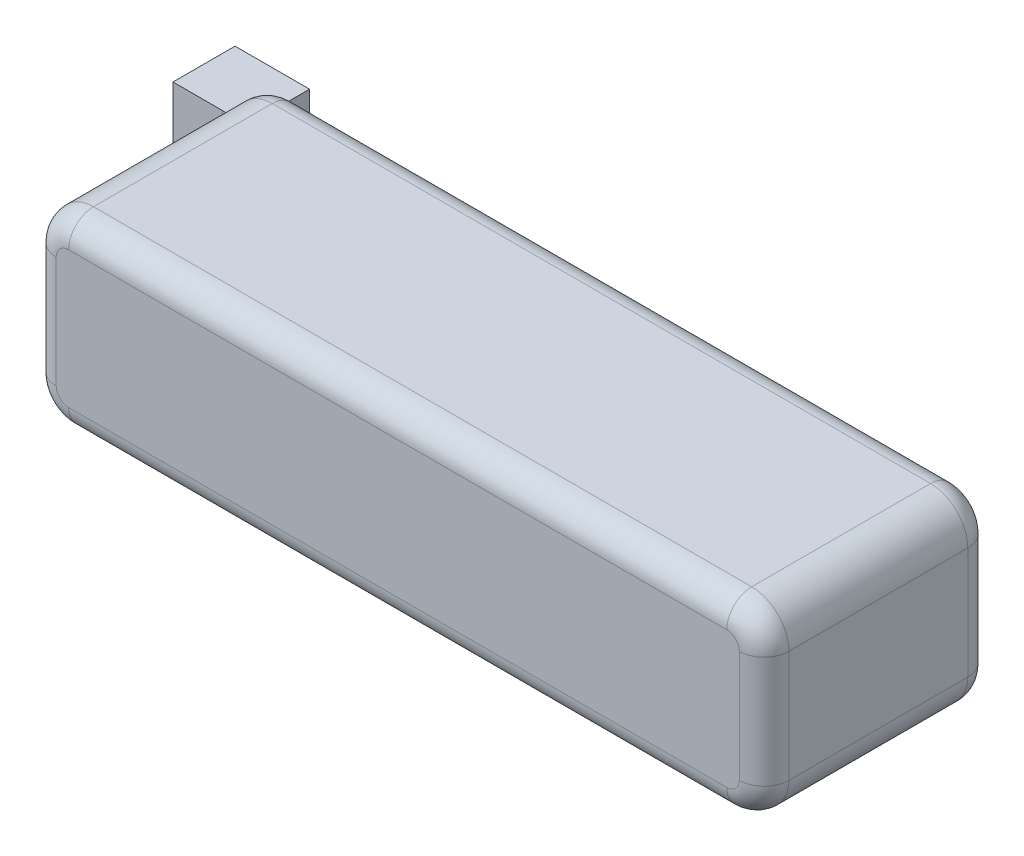
SolidWorks part; units mm, degrees
material "Polyurethane Foam Flexible"
ref_plane "Front Plane" through (0, 0, 0) normal (0, 0, 1) x (1, 0, 0)
ref_plane "Top Plane" through (0, 0, 0) normal (0, 1, 0) x (1, 0, 0)
ref_plane "Right Plane" through (0, 0, 0) normal (1, 0, 0) x (0, 0, -1)
sketch "Sketch1" plane through (0, 0, 0) normal (0, 1, 0) x (1, 0, 0)
  line L1 (0, 0) -> (74.93, 0)
  line L2 (0, 0) -> (0, -23.368)
  line L3 (0, -23.368) -> (74.93, -23.368)
  line L4 (74.93, 0) -> (74.93, -23.368)
  dimension "D1" = 74.93
  dimension "D2" = 23.368
extrude "Boss-Extrude1" add sketch "Sketch1" along normal blind 19.05
sketch "Sketch2" plane through (0, 0, 0) normal (-1, 0, 0) x (0, 0, 1)
  line L0 (0, 19.05) -> (0, 0) construction
  line L1 (0, 14.605) -> (1.27, 14.605)
  line L2 (0, 14.605) -> (0, 4.445)
  line L3 (0, 4.445) -> (1.27, 4.445)
  line L4 (1.27, 14.605) -> (1.27, 4.445)
  line L5 (3.34, 19.05) -> (3.34, 14.605) construction
  line L6 (0, 19.05) -> (23.368, 19.05) construction
  line L7 (3.34, 4.445) -> (3.34, 0) construction
  line L8 (0, 0) -> (23.368, 0) construction
  line L10 (0, 14.605) -> (-5.08, 14.605)
  line L11 (0, 14.605) -> (0, 4.445)
  line L12 (0, 4.445) -> (-5.08, 4.445)
  line L13 (-5.08, 14.605) -> (-5.08, 4.445)
  line M4 (0, 19.05) -> (0, 0)
  dimension "D1" = 10.16
  dimension "D2" = 5.08
  dimension "D3" = 1.27
extrude "Boss-Extrude2" add sketch "Sketch2" along normal blind 7.62 contours L10 L13 L12 M4 | L4 L1 L3 M4 region at (0, 9.525, 0.635) region at (0, 9.525, -2.54)
fillet "Fillet1" radius 2.54 2 edges at (0, 9.525, 1.27) (0, 9.525, 0)
fillet "Fillet2" radius 3.81 4 edges at (0, 19.05, 11.684) (74.93, 19.05, 11.684) (74.93, 0, 11.684) (0, 0, 11.684)
fillet "Fillet3" radius 2.54 8 edges at (1.1159, 1.1159, 23.368) (0, 9.525, 23.368) (1.1159, 17.9341, 23.368) (37.465, 19.05, 23.368) (73.8141, 17.9341, 23.368) (74.93, 9.525, 23.368) (73.8141, 1.1159, 23.368) (37.465, 0, 23.368)
fillet "Fillet4" radius 2.54 9 edges at (0, 14.9225, 0) (1.1159, 17.9341, 0) (37.465, 19.05, 0) (73.8141, 17.9341, 0) (74.93, 9.525, 0) (73.8141, 1.1159, 0) (0, 4.1275, 0) (1.1159, 1.1159, 0) (37.465, 0, 0)
